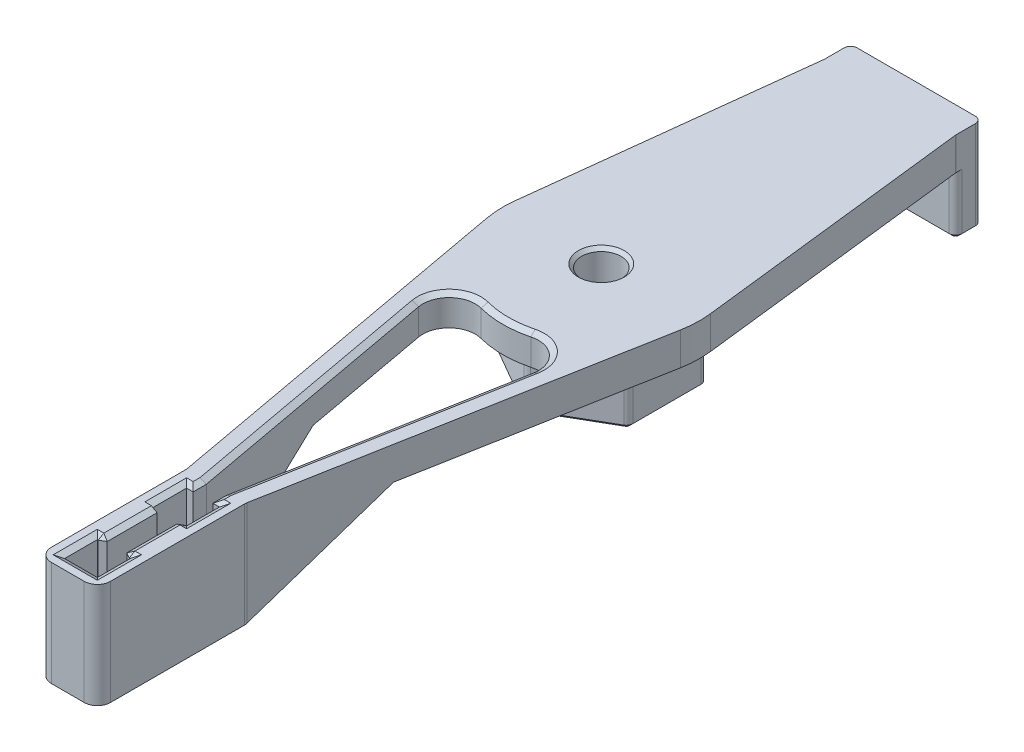
SolidWorks part; units mm, degrees
ref_plane "Front Plane" through (0, 0, 0) normal (0, 0, 1) x (1, 0, 0)
ref_plane "Top Plane" through (0, 0, 0) normal (0, 1, 0) x (1, 0, 0)
ref_plane "Right Plane" through (0, 0, 0) normal (1, 0, 0) x (0, 0, -1)
sketch "Sketch1" plane through (0, 0, 0) normal (0, 1, 0) x (1, 0, 0)
  circle A0 centre (0, 0) radius 15
  dimension "D1" = 30
extrude "Boss-Extrude1" add sketch "Sketch1" along normal blind 5
sketch "Sketch2" plane through (0, 0, 0) normal (0, -1, 0) x (1, 0, 0)
  line L1 (0, 11.547) -> (-10, 5.7735)
  line L2 (-10, 5.7735) -> (-10, -5.7735)
  line L3 (-10, -5.7735) -> (0, -11.547)
  line L4 (0, -11.547) -> (10, -5.7735)
  line L5 (10, -5.7735) -> (10, 5.7735)
  line L6 (10, 5.7735) -> (0, 11.547)
  circle A0 centre (0, 0) radius 10 construction
  dimension "D1" = 20
extrude "Boss-Extrude2" add sketch "Sketch2" along normal blind 9
sketch "Sketch3" plane through (0, 5, 0) normal (0, 1, 0) x (1, 0, 0)
  circle A0 centre (0, 0) radius 3
  dimension "D1" = 6
extrude "Cut-Extrude1" cut sketch "Sketch3" against normal up to next
fillet "Fillet1" radius 1 6 edges at (-10, -4.5, -5.7735) (0, -4.5, -11.547) (10, -4.5, -5.7735) (10, -4.5, 5.7735) (0, -4.5, 11.547) (-10, -4.5, 5.7735)
chamfer "Chamfer1" distance 0.5 angle 45 26 edges at (5, 0, -8.6603) (9.866, 0, -5.6962) (0, 0, -11.3923) (10, 0, 0) (-5, 0, -8.6603) (9.866, 0, 5.6962) (-9.866, 0, -5.6962) (5, 0, 8.6603) (-10, 0, 0) (0, 0, 11.3923) (-9.866, 0, 5.6962) (-5, 0, 8.6603) (5, -9, -8.6603) (9.866, -9, -5.6962) (0, -9, -11.3923) (10, -9, 0) (-5, -9, -8.6603) (9.866, -9, 5.6962) (-9.866, -9, -5.6962) (5, -9, 8.6603) (-10, -9, 0) (0, -9, 11.3923) (-9.866, -9, 5.6962) (-5, -9, 8.6603) (0, -9, -3) (0, 5, 3)
sketch "Sketch4" plane through (0, 5, 0) normal (0, 1, 0) x (1, 0, 0)
  line L0 (0, 46) -> (0, 0) construction
  line L1 (10, 48) -> (-10, 48)
  line L2 (10, 48) -> (10, 44)
  line L3 (10, 44) -> (-10, 44) construction
  line L4 (-10, 48) -> (-10, 44)
  line L5 (10, 48) -> (-10, 44) construction
  line L6 (10, 44) -> (-10, 48) construction
  line L7 (-10, 44) -> (-14.9002, 1.7272)
  line L8 (10, 44) -> (14.9002, 1.7272)
  circle A0 centre (0, 0) radius 15 construction
  arc A1 (14.9002, 1.7272) -> (-14.9002, 1.7272) centre (0, 0) ccw
  point P0 (0, 46)
  dimension "D1" = 20
  dimension "D2" = 4
  dimension "D3" = 46
extrude "Boss-Extrude3" add sketch "Sketch4" against normal up to surface (5 mm away) up to face at (0, 0, 0)
sketch "Sketch5" plane through (0, 0, 0) normal (0, -1, 0) x (1, 0, 0)
  line L1 (-10, -48) -> (10, -48)
  line L2 (-10, -48) -> (-10, -44)
  line L3 (-10, -44) -> (10, -44)
  line L4 (10, -48) -> (10, -44)
extrude "Boss-Extrude4" add sketch "Sketch5" along normal up to surface (9 mm away) up to face at (0, -9, -3.5)
fillet "Fillet2" radius 1 4 edges at (-10, -4.5, -44) (10, -4.5, -44) (10, -2, -48) (-10, -2, -48)
chamfer "Chamfer3" distance 0.5 angle 45 8 edges at (9.7071, -9, -44.2929) (10, -9, -46) (9.7071, -9, -47.7071) (0, -9, -48) (-9.7071, -9, -47.7071) (-10, -9, -46) (-9.7071, -9, -44.2929) (0, -9, -44)
fillet "Fillet3" radius 1 2 edges at (-10, 2.5, -44) (10, 2.5, -44)
sketch "Sketch6" plane through (0, 5, 0) normal (0, 1, 0) x (1, 0, 0)
  line L0 (0, 0) -> (0, -70) construction
  line L1 (2.5, -60.7) -> (-2.5, -60.7) construction
  line L2 (2.5, -60.7) -> (2.5, -79.3) construction
  line L3 (2.5, -79.3) -> (-2.5, -79.3) construction
  line L4 (-2.5, -60.7) -> (-2.5, -79.3) construction
  line L5 (2.5, -60.7) -> (-2.5, -79.3) construction
  line L6 (2.5, -79.3) -> (-2.5, -60.7) construction
  line L7 (4.5, -58.7) -> (4.5, -81.3)
  line L8 (4.5, -81.3) -> (-4.5, -81.3)
  line L9 (-4.5, -58.7) -> (-4.5, -81.3)
  line L10 (-4.5, -58.7) -> (-14.7546, -2.7019)
  line L11 (4.5, -58.7) -> (14.7546, -2.7019)
  line L12 (-4.5, -58.7) -> (4.5, -58.7) construction
  line L13 (-4.5, -60.7) -> (-4.5, -81.3) construction
  line L14 (4.5, -60.7) -> (4.5, -81.3) construction
  arc A0 (-14.9002, 1.7272) -> (14.9002, 1.7272) centre (0, 0) ccw construction
  arc A1 (-14.7546, -2.7019) -> (14.7546, -2.7019) centre (0, 0) ccw
  point P0 (0, -70)
  dimension "D1" = 5
  dimension "D2" = 18.6
  dimension "D3" = 70
  dimension "D4" = 2
  dimension "D5" = 2
extrude "Boss-Extrude5" add sketch "Sketch6" against normal up to surface (5 mm away) up to face at (0, 0, 0)
sketch "Sketch7" plane through (0, 0, 0) normal (0, -1, 0) x (1, 0, 0)
  line L1 (-4.5, 81.3) -> (4.5, 81.3)
  line L2 (-4.5, 81.3) -> (-4.5, 58.7)
  line L3 (-4.5, 58.7) -> (4.5, 58.7)
  line L4 (4.5, 81.3) -> (4.5, 58.7)
extrude "Boss-Extrude6" add sketch "Sketch7" along normal blind 11
sketch "Sketch8" plane through (0, -11, 0) normal (0, -1, 0) x (1, 0, 0)
  line L8 (-2.5, 79.3) -> (-2.5, 60.7)
  line L9 (-2.5, 60.7) -> (2.5, 60.7)
  line L10 (2.5, 60.7) -> (2.5, 79.3)
  line L11 (2.5, 79.3) -> (-2.5, 79.3)
  line L12 (-2.5, 79.3) -> (-2.5, 60.7)
  line L13 (-2.5, 60.7) -> (2.5, 60.7)
  line L14 (2.5, 60.7) -> (2.5, 79.3)
  line L15 (2.5, 79.3) -> (-2.5, 79.3)
  dimension "D1" = 2
extrude "Cut-Extrude2" cut sketch "Sketch8" against normal blind 3
sketch "Sketch10" plane through (0, -8, 0) normal (0, -1, 0) x (1, 0, 0)
  line L0 (2.5, 60.7) -> (2.5, 79.3) construction
  line L1 (-2.5, 79.3) -> (2.5, 79.3)
  line L2 (-2.5, 79.3) -> (-2.5, 74.3)
  line L3 (-2.5, 74.3) -> (2.5, 74.3)
  line L4 (2.5, 79.3) -> (2.5, 74.3)
  line L5 (-2.5, 79.3) -> (-2.5, 60.7) construction
  line L6 (2.5, 60.7) -> (-2.5, 60.7)
  line L7 (2.5, 60.7) -> (2.5, 65.7)
  line L8 (2.5, 65.7) -> (-2.5, 65.7)
  line L9 (-2.5, 60.7) -> (-2.5, 65.7)
  dimension "D1" = 5
extrude "Cut-Extrude4" cut sketch "Sketch10" against normal up to next
sketch "Sketch11" plane through (0, -11, 0) normal (0, -1, 0) x (1, 0, 0)
  line L0 (0, 0) -> (0, 79.3) construction
  line L1 (2.5, 79.3) -> (-2.5, 79.3) construction
  line L2 (-1.5, 74.3) -> (-1.5, 58.7)
  line L3 (-2.5, 74.3) -> (2.5, 74.3) construction
  line L4 (-4.5, 58.7) -> (4.5, 58.7) construction
  line L5 (1.5, 74.3) -> (1.5, 58.7)
  line L6 (-1.5, 58.7) -> (-10.2427, 10.9585)
  line L7 (1.5, 58.7) -> (10.2427, 10.9585)
  line L10 (-4.5, 58.7) -> (-14.7546, 2.7019) construction
  line L11 (-4.5, 58.7) -> (4.5, 58.7) construction
  line L12 (-1.5, 74.3) -> (1.5, 74.3)
  arc A0 (10.2427, 10.9585) -> (-10.2427, 10.9585) centre (0, 0) ccw
  arc A1 (-14.7546, 2.7019) -> (-14.9002, -1.7272) centre (0, 0) ccw construction
  dimension "D1" = 3
extrude "Cut-Extrude5" cut sketch "Sketch11" against normal up to surface (16 mm away) up to face at (0, 5, 76.8)
chamfer "Chamfer5" distance 11 angle 60 2 edges at (3, 0, 58.7) (-3, 0, 58.7)
fillet "Fillet4" radius 4 2 edges at (10.2427, 2.5, 10.9585) (-10.2427, 2.5, 10.9585)
chamfer "Chamfer6" distance 0.5 angle 60 36 edges at (2, -11, 60.7) (2.5, -11, 70) (0, -11, 79.3) (-2, -11, 60.7) (-2.5, -11, 70) (0, 5, 79.3) (-2.5, 5, 76.8) (-2, 5, 74.3) (-1.5, 5, 70) (-2, 5, 65.7) (-2.5, 5, 63.2) (-2, 5, 60.7) (-1.5, -11, 59.7) (-1.5, 5, 59.7) (-5.1259, 5, 38.8998) (0, 0, 15) (0, 5, 15) (5.1259, 5, 38.8998) (1.5, 5, 59.7) (1.5, -11, 59.7) (2, 5, 60.7) (2.5, 5, 63.2) (2, 5, 65.7) (1.5, 5, 70) (2, 5, 74.3) (2.5, 5, 76.8) (6.8704, 0, 29.3736) (-6.8704, 0, 29.3736) (-1.5, -1.5, 74.3) (1.5, -1.5, 74.3) (1.5, -1.5, 65.7) (-1.5, -1.5, 65.7) (7.5373, 5, 15.4464) (7.5373, 0, 15.4464) (-7.5373, 5, 15.4464) (-7.5373, 0, 15.4464)
fillet "Fillet5" radius 2 4 edges at (-4.5, -3, 58.7) (4.5, -3, 58.7) (-4.5, -3, 81.3) (4.5, -3, 81.3)
